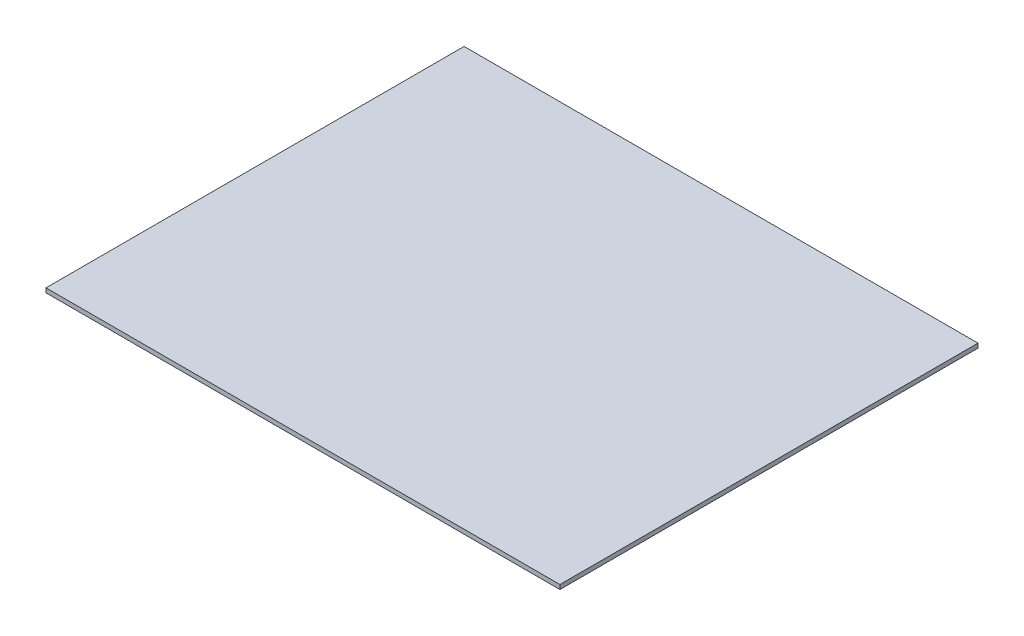
SolidWorks part; units mm, degrees
material "Acrylic (Medium-high impact)"
ref_plane "Front Plane" through (0, 0, 0) normal (0, 0, 1) x (1, 0, 0)
ref_plane "Top Plane" through (0, 0, 0) normal (0, 1, 0) x (1, 0, 0)
ref_plane "Right Plane" through (0, 0, 0) normal (1, 0, 0) x (0, 0, -1)
sketch "Sketch1" plane through (0, 0, 0) normal (0, 1, 0) x (1, 0, 0)
  line L1 (-187.325, -152.4) -> (187.325, -152.4)
  line L2 (-187.325, -152.4) -> (-187.325, 152.4)
  line L3 (-187.325, 152.4) -> (187.325, 152.4)
  line L4 (187.325, -152.4) -> (187.325, 152.4)
  line L5 (-187.325, -152.4) -> (187.325, 152.4) construction
  line L6 (-187.325, 152.4) -> (187.325, -152.4) construction
  point P0 (0, 0)
  dimension "D1" = 304.8
  dimension "D2" = 374.65
extrude "Boss-Extrude1" add sketch "Sketch1" along normal blind 3.175
